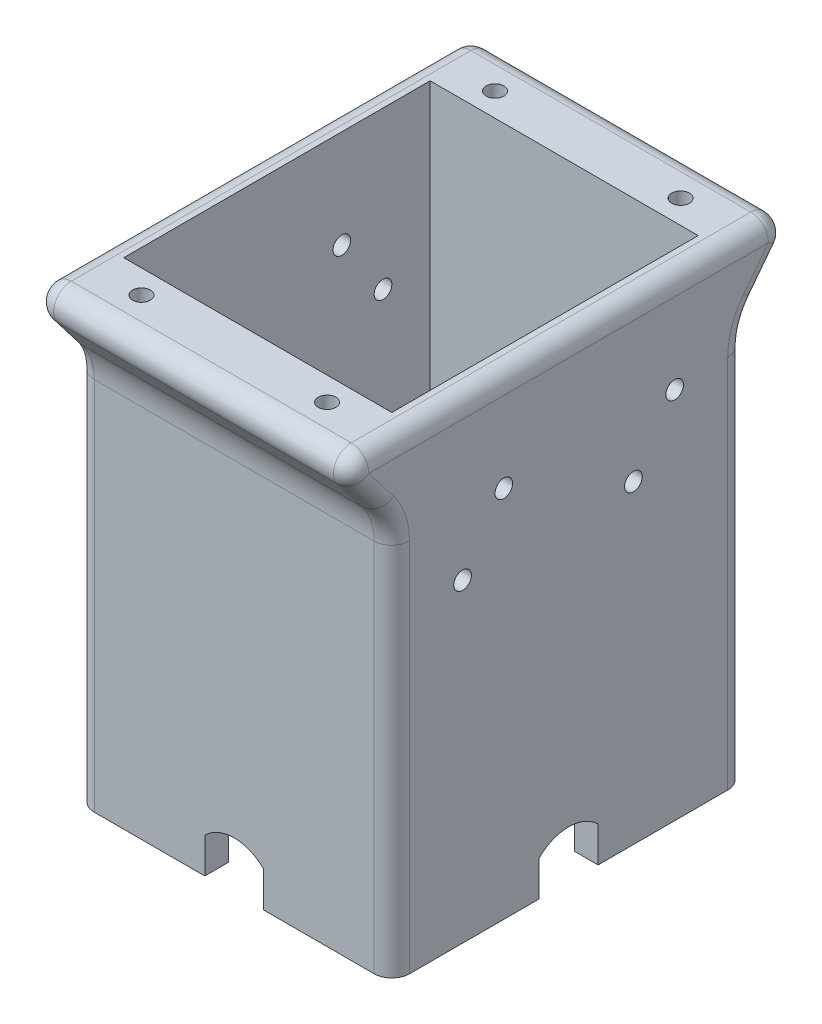
SolidWorks part; units mm, degrees
ref_plane "Front Plane" through (0, 0, 0) normal (0, 0, 1) x (1, 0, 0)
ref_plane "Top Plane" through (0, 0, 0) normal (0, 1, 0) x (1, 0, 0)
ref_plane "Right Plane" through (0, 0, 0) normal (1, 0, 0) x (0, 0, -1)
sketch "Sketch1" plane through (0, 0, 0) normal (0, 1, 0) x (1, 0, 0)
  line L1 (-26.75, 30) -> (26.75, 30)
  line L2 (-26.75, 30) -> (-26.75, -30)
  line L3 (-26.75, -30) -> (26.75, -30)
  line L4 (26.75, 30) -> (26.75, -30)
  line L5 (-26.75, 30) -> (26.75, -30) construction
  line L6 (-26.75, -30) -> (26.75, 30) construction
  line L7 (-22.75, 26) -> (22.75, 26)
  line L8 (-22.75, 26) -> (-22.75, -26)
  line L9 (-22.75, -26) -> (22.75, -26)
  line L10 (22.75, 26) -> (22.75, -26)
  line L11 (-22.75, 26) -> (22.75, -26) construction
  line L12 (-22.75, -26) -> (22.75, 26) construction
  point P0 (0, 0)
  point P6 (0, 0)
  dimension "D1" = 45.5
  dimension "D2" = 4
  dimension "D3" = 4
extrude "Boss-Extrude1" add sketch "Sketch1" along normal blind 80
sketch "Sketch3" plane through (-26.75, 0, 0) normal (-1, 0, 0) x (0, 0, 1)
  line L0 (-30, 80) -> (30, 80) construction
  circle A0 centre (18, 63.35) radius 1.5
  circle A1 centre (11, 53.35) radius 1.5
  dimension "D1" = 3
  dimension "D3" = 3
  dimension "D2" = 16.65
  dimension "D4" = 10
  dimension "D5" = 7
  dimension "D6" = 8
extrude "Cut-Extrude1" cut sketch "Sketch3" against normal blind 4 and the other way through all
pattern_linear "LPattern1" count 2 spacing 29 along (0, 0, -1) of "Cut-Extrude1"
sketch "Sketch4" plane through (26.75, 0, 0) normal (1, 0, 0) x (0, 0, -1)
  line L0 (-30, 80) -> (30, 80) construction
  circle A0 centre (-11, 63.35) radius 1.5
  circle A1 centre (-18, 53.35) radius 1.5
  dimension "D1" = 3
  dimension "D2" = 3
  dimension "D3" = 10
  dimension "D4" = 7
  dimension "D5" = 16.65
  dimension "D6" = 8
extrude "Cut-Extrude2" cut sketch "Sketch4" against normal blind 4
pattern_linear "LPattern2" count 2 spacing 29 along (0, 0, -1) of "Cut-Extrude2"
sketch "Sketch5" plane through (-26.75, 0, 0) normal (-1, 0, 0) x (0, 0, 1)
  line L0 (30, 80) -> (30, 67)
  line L1 (30, 80) -> (30, 0) construction
  line L2 (30, 67) -> (40, 80)
  line L3 (40, 80) -> (30, 80)
  line L4 (-30, 80) -> (-30, 67)
  line L5 (-30, 80) -> (-30, 0) construction
  line L6 (-30, 67) -> (-40, 80)
  line L7 (-30, 80) -> (-40, 80)
  dimension "D1" = 10
  dimension "D2" = 13
extrude "Boss-Extrude2" add sketch "Sketch5" against normal through all
fillet "Fillet1" radius 10 2 edges at (0, 67, 30) (0, 67, -30)
fillet "Fillet2" radius 3 16 edges at (26.75, 31.7994, -30) (26.75, 66.8188, -30.5326) (26.75, 74.8479, -36.0369) (26.75, 80, 0) (0, 80, -40) (26.75, 31.7994, 30) (26.75, 66.8188, 30.5326) (-26.75, 31.7994, 30) (-26.75, 66.8188, 30.5326) (-26.75, 31.7994, -30) (-26.75, 66.8188, -30.5326) (26.75, 74.8479, 36.0369) (0, 80, 40) (-26.75, 74.8479, 36.0369) (-26.75, 74.8479, -36.0369) (-26.75, 80, 0)
sketch "Sketch6" plane through (0, 80, 0) normal (0, 1, 0) x (1, 0, 0)
  line L0 (-22.75, -26) -> (22.75, -26) construction
  line L2 (-23.75, 33.9074) -> (-23.75, -33.9074) construction
  line L3 (0, -33.9074) -> (0, -26) construction
  line L4 (-23.75, -33.9074) -> (23.75, -33.9074) construction
  circle A0 centre (-15.75, -30) radius 1.5
  circle A1 centre (15.75, -30) radius 1.5
  dimension "D2" = 3
  dimension "D1" = 4
  dimension "D3" = 8
extrude "Cut-Extrude3" cut sketch "Sketch6" against normal blind 9
ref_plane "Plane1" through (0, 0, 0) normal (0, 0, 1) x (1, 0, 0)
mirror "Mirror1" about plane through (0, 0, 0) normal (0, 0, 1) of "Cut-Extrude3"
sketch "Sketch7" plane through (26.75, 0, 0) normal (1, 0, 0) x (0, 0, -1)
  line L0 (5, 0) -> (5, 6)
  line L1 (-27, 0) -> (27, 0) construction
  line L2 (-5, 0) -> (-5, 6)
  line L3 (5, 0) -> (-5, 0)
  arc A0 (-5, 6) -> (5, 6) centre (0, 1.101) cw
  dimension "D5" = 7
  dimension "D1" = 6
  dimension "D2" = 6
  dimension "D3" = 5
  dimension "D4" = 5
extrude "Cut-Extrude4" cut sketch "Sketch7" against normal through all
sketch "Sketch8" plane through (0, 0, -30) normal (0, 0, -1) x (-1, 0, 0)
  line L0 (5, 0) -> (5, 6)
  line L1 (-23.75, 0) -> (23.75, 0) construction
  line L2 (-5, 0) -> (-5, 6)
  line L3 (5, 0) -> (-5, 0)
  arc A0 (-5, 6) -> (5, 6) centre (0, 1.101) cw
  dimension "D5" = 7
  dimension "D1" = 6
  dimension "D2" = 6
  dimension "D3" = 5
  dimension "D4" = 5
extrude "Cut-Extrude5" cut sketch "Sketch8" against normal through all
